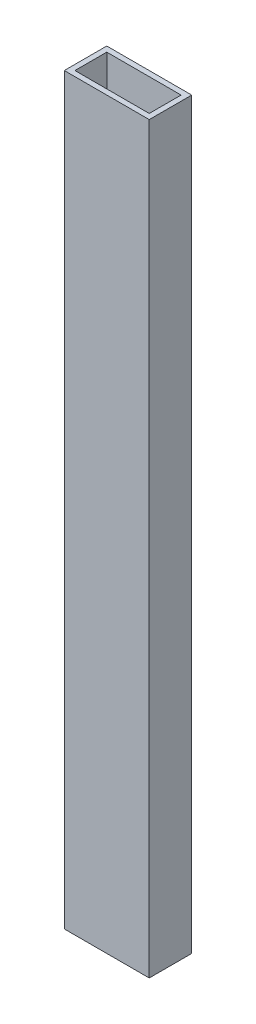
SolidWorks part; units mm, degrees
ref_plane "Front Plane" through (0, 0, 0) normal (0, 0, 1) x (1, 0, 0)
ref_plane "Top Plane" through (0, 0, 0) normal (0, 1, 0) x (1, 0, 0)
ref_plane "Right Plane" through (0, 0, 0) normal (1, 0, 0) x (0, 0, -1)
sketch "Sketch1" plane through (0, 0, 0) normal (0, 1, 0) x (1, 0, 0)
  line L0 (3.175, 3.175) -> (3.175, 22.225)
  line L1 (0, 0) -> (50.8, 0)
  line L2 (0, 0) -> (0, 25.4)
  line L3 (0, 25.4) -> (50.8, 25.4)
  line L4 (50.8, 0) -> (50.8, 25.4)
  line L5 (3.175, 22.225) -> (47.625, 22.225)
  line L6 (47.625, 3.175) -> (47.625, 22.225)
  line L7 (3.175, 3.175) -> (47.625, 3.175)
  dimension "D1" = 50.8
  dimension "D2" = 25.4
  dimension "D3" = 3.175
extrude "Boss-Extrude1" add sketch "Sketch1" along normal blind 444.5
